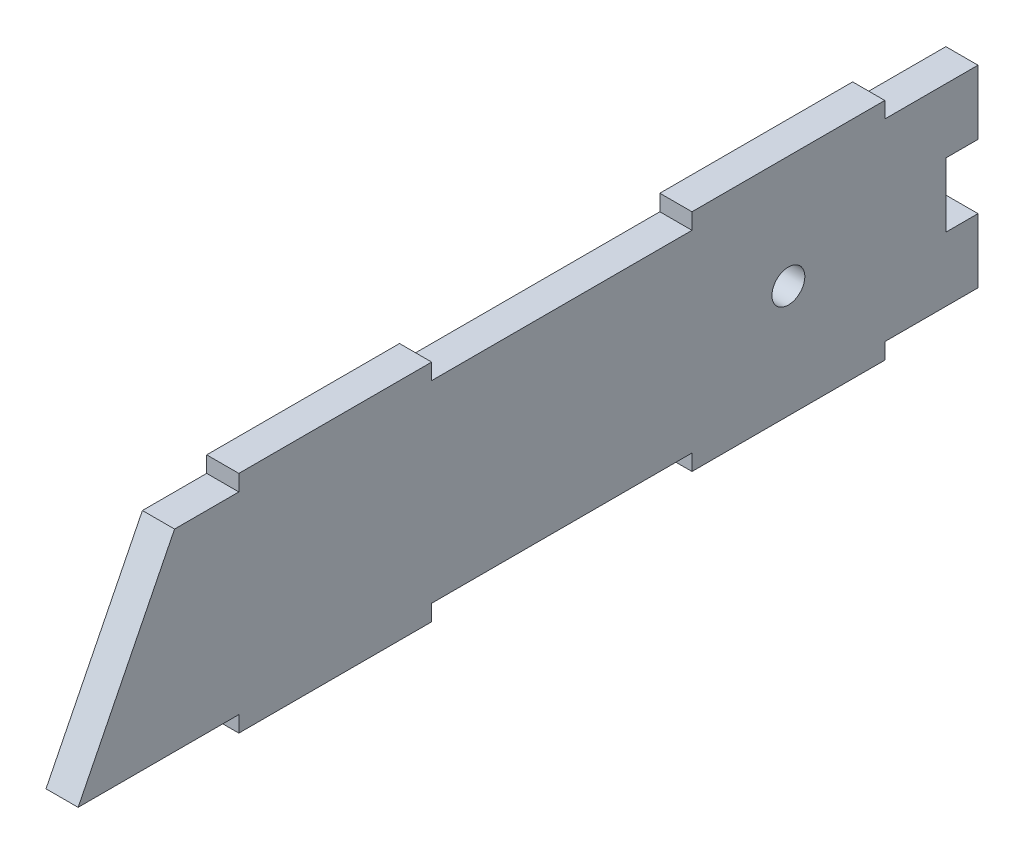
SolidWorks part; units mm, degrees
material "7050-T73510"
ref_plane "Front Plane" through (0, 0, 0) normal (0, 0, 1) x (1, 0, 0)
ref_plane "Top Plane" through (0, 0, 0) normal (0, 1, 0) x (1, 0, 0)
ref_plane "Right Plane" through (0, 0, 0) normal (1, 0, 0) x (0, 0, -1)
sketch "Sketch1" plane through (0, 0, 0) normal (1, 0, 0) x (0, 0, -1)
  line L1 (-177.8, -38.1) -> (177.8, -38.1)
  line L2 (-177.8, -38.1) -> (-177.8, 38.1)
  line L3 (-177.8, 38.1) -> (177.8, 38.1)
  line L4 (177.8, -38.1) -> (177.8, 38.1)
  line L5 (-177.8, -38.1) -> (177.8, 38.1) construction
  line L6 (-177.8, 38.1) -> (177.8, -38.1) construction
  point P0 (0, 0)
  dimension "D1" = 355.6
  dimension "D2" = 76.2
extrude "Boss-Extrude1" add sketch "Sketch1" along normal blind 12.7
sketch "Sketch2" plane through (12.7, 0, 0) normal (1, 0, 0) x (0, 0, -1)
  line L0 (-177.8, -38.1) -> (-139.7, 38.1)
  line L1 (177.8, 38.1) -> (-177.8, 38.1) construction
  dimension "D1" = 38.1
extrude "Cut-Extrude1" cut sketch "Sketch2" against normal through all and the other way through all
sketch "Sketch3" plane through (0, 0, 0) normal (-1, 0, 0) x (0, 0, 1)
  line L0 (177.8, -38.1) -> (-177.8, -38.1) construction
  line L1 (-140.97, -38.1) -> (-64.77, -38.1)
  line L2 (-140.97, -38.1) -> (-140.97, -44.45)
  line L3 (-140.97, -44.45) -> (-64.77, -44.45)
  line L4 (-64.77, -38.1) -> (-64.77, -44.45)
  line L5 (-177.8, -38.1) -> (-177.8, 38.1) construction
  line L6 (38.1, -38.1) -> (114.3, -38.1)
  line L7 (38.1, -38.1) -> (38.1, -44.45)
  line L8 (38.1, -44.45) -> (114.3, -44.45)
  line L9 (114.3, -38.1) -> (114.3, -44.45)
  line L10 (-177.8, 38.1) -> (139.7, 38.1) construction
  line L11 (-140.97, 38.1) -> (-64.77, 38.1)
  line L12 (-140.97, 38.1) -> (-140.97, 44.45)
  line L13 (-140.97, 44.45) -> (-64.77, 44.45)
  line L14 (-64.77, 38.1) -> (-64.77, 44.45)
  line L16 (38.1, 38.1) -> (114.3, 38.1)
  line L17 (38.1, 38.1) -> (38.1, 44.45)
  line L18 (38.1, 44.45) -> (114.3, 44.45)
  line L19 (114.3, 38.1) -> (114.3, 44.45)
  dimension "D1" = 76.2
  dimension "D2" = 6.35
  dimension "D3" = 76.2
  dimension "D4" = 6.35
  dimension "D5" = 36.83
  dimension "D6" = 215.9
  dimension "D7" = 76.2
  dimension "D8" = 6.35
  dimension "D9" = 6.35
  dimension "D10" = 76.2
extrude "Boss-Extrude2" add sketch "Sketch3" against normal blind 12.7
sketch "Sketch4" plane through (0, 0, 0) normal (-1, 0, 0) x (0, 0, 1)
  line L0 (-177.8, -38.1) -> (-177.8, 38.1) construction
  line L1 (-177.8, 12.7) -> (-165.1, 12.7)
  line L2 (-177.8, 12.7) -> (-177.8, -12.7)
  line L3 (-177.8, -12.7) -> (-165.1, -12.7)
  line L4 (-165.1, 12.7) -> (-165.1, -12.7)
  line L5 (-140.97, -38.1) -> (-177.8, -38.1) construction
  line L6 (-177.8, 38.1) -> (-140.97, 38.1) construction
  dimension "D1" = 25.4
  dimension "D2" = 25.4
  dimension "D3" = 12.7
extrude "Cut-Extrude2" cut sketch "Sketch4" against normal through all
sketch "Sketch5" plane through (0, 0, 0) normal (-1, 0, 0) x (0, 0, 1)
  line L0 (-165.1, -12.7) -> (-165.1, 12.7) construction
  line L1 (-140.97, -38.1) -> (-177.8, -38.1) construction
  circle A0 centre (-102.87, 0) radius 6.5
  dimension "D1" = 62.23
  dimension "D3" = 13
  dimension "D2" = 38.1
extrude "Cut-Extrude3" cut sketch "Sketch5" against normal through all
